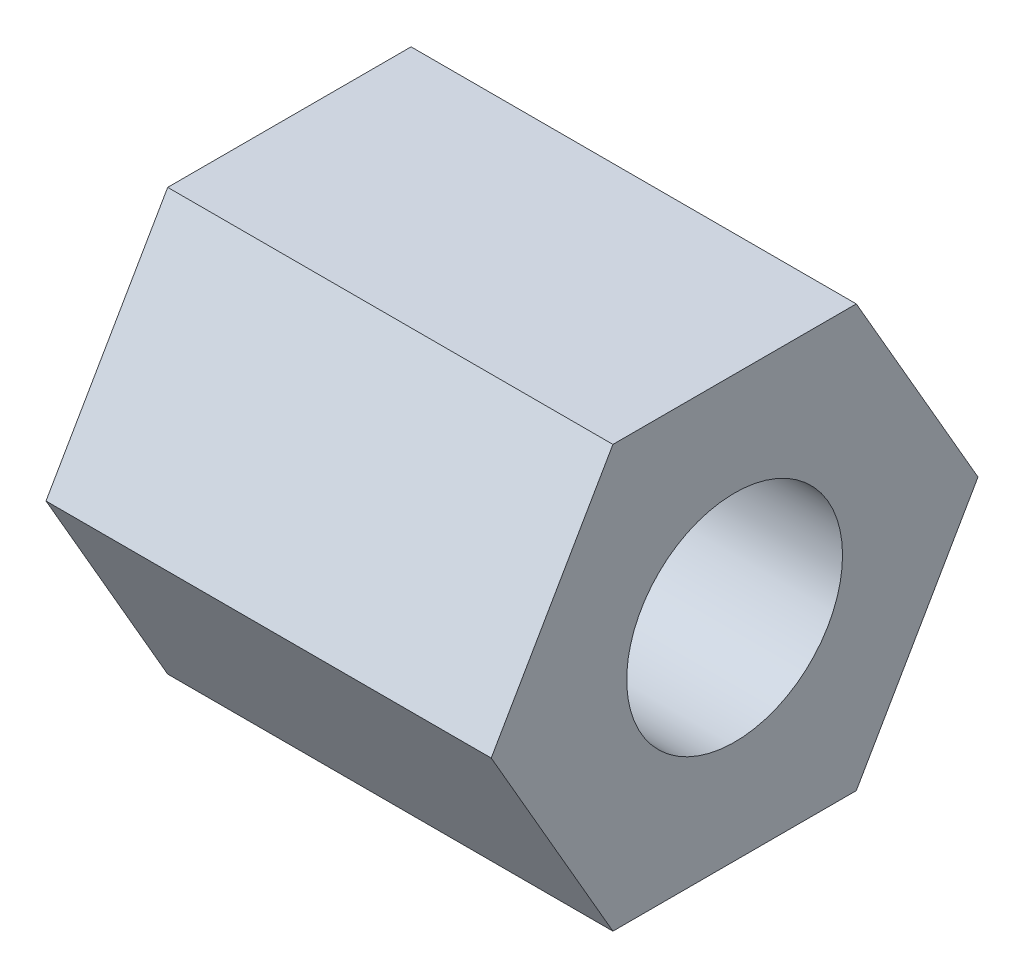
SolidWorks part; units mm, degrees
material "6061-T4 (SS)"
ref_plane "Front Plane" through (0, 0, 0) normal (0, 0, 1) x (1, 0, 0)
ref_plane "Top Plane" through (0, 0, 0) normal (0, 1, 0) x (1, 0, 0)
ref_plane "Right Plane" through (0, 0, 0) normal (1, 0, 0) x (0, 0, -1)
sketch "Sketch1" plane through (0, 0, 0) normal (1, 0, 0) x (0, 0, -1)
  line L0 (0, 0) -> (2.7496, 0) construction
  line L1 (2.7496, 0) -> (1.3748, 2.3812)
  line L2 (1.3748, 2.3812) -> (-1.3748, 2.3813)
  line L3 (-1.3748, 2.3813) -> (-2.7496, 0)
  line L4 (-2.7496, 0) -> (-1.3748, -2.3813)
  line L5 (-1.3748, -2.3813) -> (1.3748, -2.3813)
  line L6 (1.3748, -2.3813) -> (2.7496, 0)
  circle A0 centre (0, 0) radius 2.3812 construction
  point P1 (-2.0622, 1.1906)
  dimension "D1" = 4.7625
extrude "Boss-Extrude1" add sketch "Sketch1" along normal blind 5.03
sketch "Sketch2" plane through (5.03, 0, 0) normal (1, 0, 0) x (0, 0, -1)
  circle A0 centre (0, 0) radius 1.0922
  dimension "D1" = 2.1844
hole_wizard "#2 Clearance Hole1" positions "Sketch3" profile "Sketch4" hole size "#2" standard "ANSI Inch" end condition through all
sketch "Sketch3" plane through (5.03, 0, 0) normal (1, 0, 0) x (0, 0, -1)
  point P0 (0, 0)
sketch "Sketch4" plane through (5.03, 0, 0) normal (0, 1, 0) x (0, 0, -1)
  line L0 (0, 0) -> (0, 5.03)
  line L1 (0, 5.03) -> (1.2192, 5.03)
  line L2 (1.2192, 5.03) -> (1.2192, 0)
  line L5 (1.2192, 0) -> (0, 0)
  line L11 (0, -6.35) -> (0, 107.95) construction
  dimension "Thru Hole Dia." = 2.4384
  dimension "Thru Hole Depth" = 5.03
